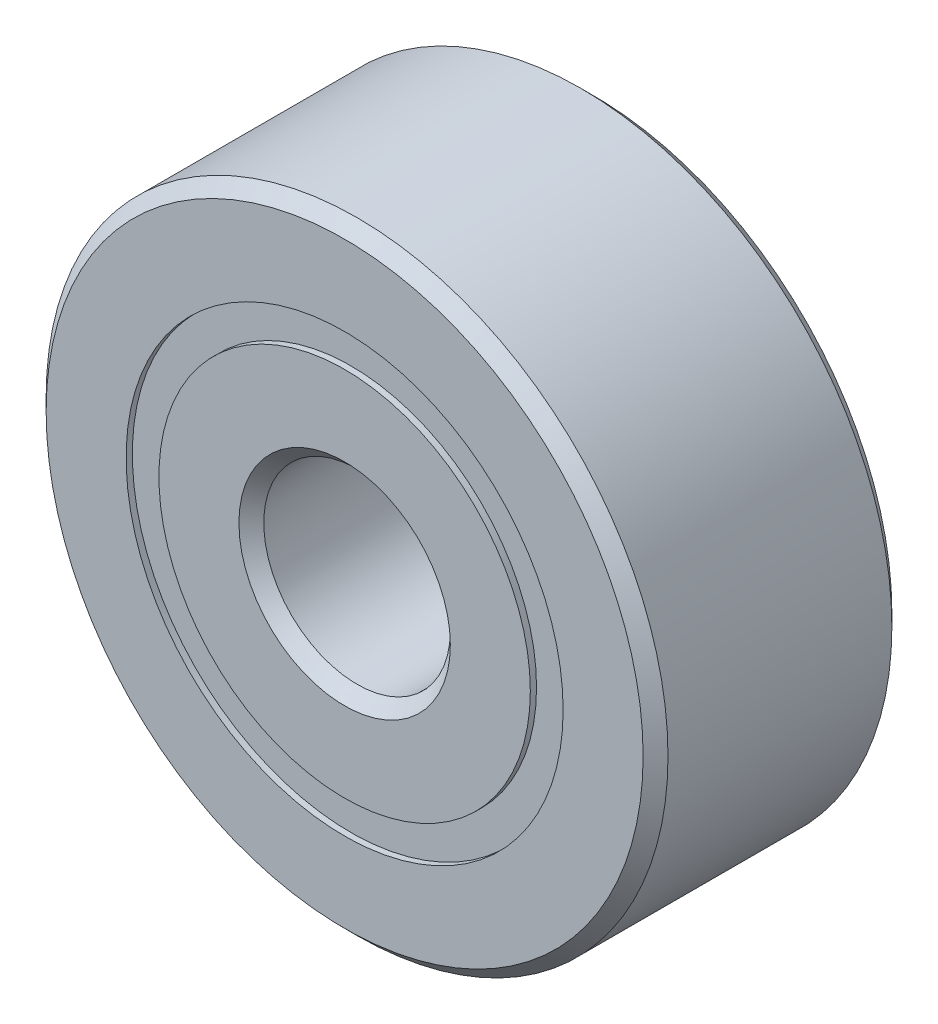
SolidWorks part; units mm, degrees
ref_plane "Front Plane" through (0, 0, 0) normal (0, 0, 1) x (1, 0, 0)
ref_plane "Top Plane" through (0, 0, 0) normal (0, 1, 0) x (1, 0, 0)
ref_plane "Right Plane" through (0, 0, 0) normal (1, 0, 0) x (0, 0, -1)
sketch "Sketch1" plane through (0, 0, 0) normal (1, 0, 0) x (0, 0, -1)
  line L0 (-2, 0) -> (2, 0) construction
  line L1 (0, 5) -> (0, -5) construction
  line L2 (1.8, 5) -> (-1.8, 5)
  line L3 (-1.8, 5) -> (-2, 4.8)
  line L4 (-2, 4.8) -> (-2, 3.5137)
  line L5 (-2, 3.5137) -> (-0.8889, 3.5137)
  line L6 (2, 3.5137) -> (0.8889, 3.5137)
  line L7 (2, 4.8) -> (2, 3.5137)
  line L8 (1.8, 5) -> (2, 4.8)
  line L9 (0, 5) -> (0, 3.25) construction
  line L10 (0, 3.25) -> (0, 1.5) construction
  arc A0 (-0.8889, 3.5137) -> (0.8889, 3.5137) centre (0, 3.25) cw
  point P14 (0, 1.5)
  dimension "D3" = 1.7778
  dimension "D1" = 45
  dimension "Width" = 4
  dimension "OD" = 10
  dimension "D2" = 0.2
  dimension "Shaft Dia" = 3
  dimension "D4" = 0.2637
revolve "Revolve1" add sketch "Sketch1" angle 360 about L0
sketch "Sketch3" plane through (0, 0, 0) normal (1, 0, 0) x (0, 0, -1)
  line L0 (-2, 2.9863) -> (-0.8889, 2.9863)
  line L1 (0, 5) -> (0, -5) construction
  line L2 (-2, 4.8) -> (-2, 3.5137) construction
  line L3 (-2, 2.9863) -> (-2, 1.7)
  line L4 (-1.8, 5) -> (-2, 4.8) construction
  line L5 (-2, 1.7) -> (-1.8, 1.5)
  line L6 (-1.8, 1.5) -> (1.8, 1.5)
  line L7 (1.8, 5) -> (1.8, -5) construction
  line L8 (1.8, 1.5) -> (2, 1.7)
  line L9 (2, -4.8) -> (2, 4.8) construction
  line L10 (2, 1.7) -> (2, 2.9863)
  line L11 (2, 2.9863) -> (0.8889, 2.9863)
  line L13 (1.8, 5) -> (2, 4.8) construction
  arc A0 (0.8889, 3.5137) -> (-0.8889, 3.5137) centre (0, 3.25) ccw construction
  arc A1 (0.8889, 2.9863) -> (-0.8889, 2.9863) centre (0, 3.25) cw
revolve "Revolve3" add sketch "Sketch3" angle 360 about L0
sketch "Sketch4" plane through (0, 0, 0) normal (1, 0, 0) x (0, 0, -1)
  line L0 (-0.9272, 3.25) -> (0.9272, 3.25)
  arc A2 (-0.9272, 3.25) -> (0.9272, 3.25) centre (0, 3.25) cw
  arc A3 (0.8889, 3.5137) -> (-0.8889, 3.5137) centre (0, 3.25) ccw construction
revolve "Revolve4" add sketch "Sketch4" angle 360 about L0
ref_axis "Axis1" through (0, 0, -2) along (0, 0, 1)
pattern_circular "CirPattern1" count 12 every 30 about axis through (0, 0, -2) along (0, 0, 1) of bodies 104
sketch "Sketch5" plane through (0, 0, 0) normal (1, 0, 0) x (0, 0, -1)
  line L0 (-2, 3.5137) -> (-0.8889, 3.5137) construction
  line L1 (-1.9, 3.5137) -> (-0.9272, 3.5137)
  line L2 (-1.9, 3.5137) -> (-1.9, 2.9863)
  line L3 (-1.9, 2.9863) -> (-0.9272, 2.9863)
  line L4 (-0.9272, 3.5137) -> (-0.9272, 2.9863)
  line L5 (-2, 2.9863) -> (-0.8889, 2.9863) construction
  line L6 (2, 3.5137) -> (0.8889, 3.5137) construction
  line L7 (1.9, 3.5137) -> (0.9272, 3.5137)
  line L8 (1.9, 3.5137) -> (1.9, 2.9863)
  line L9 (1.9, 2.9863) -> (0.9272, 2.9863)
  line L10 (0.9272, 3.5137) -> (0.9272, 2.9863)
  line L11 (2, 2.9863) -> (0.8889, 2.9863) construction
  line L12 (-1.8, 5) -> (-2, 4.8) construction
  point P18 (-1.9, 4.9)
revolve "Revolve5" add sketch "Sketch5" angle 360 about L0
sketch "Sketch6" plane through (0, 0, 0) normal (1, 0, 0) x (0, 0, -1)
  line L0 (2, 0) -> (-2, 0) construction
  line L1 (2, 3.5137) -> (1.2126, 3.5137)
  line L2 (2, 3.5137) -> (2, 6.9469)
  line L3 (2, 6.9469) -> (1.2126, 6.9469)
  line L4 (1.2126, 3.5137) -> (1.2126, 6.9469)
  dimension "Th" = 0.7874
  dimension "Flange OD" = 13.8938
revolve "Revolve6" [suppressed] add sketch "Sketch6" angle 360 about L0
equation "\"D2@Sketch1\" = \"Width@Sketch1\"*.05"
equation "\"D3@Sketch1\" = \"Width@Sketch1\"/2.25"
equation "\"D4@Sketch1\" = (((\"OD@Sketch1\"-\"Width@Sketch1\")/2)/3.25)/3.5"
equation "\"D2@CirPattern1\" = 360/\"Balls@CirPattern1\""
